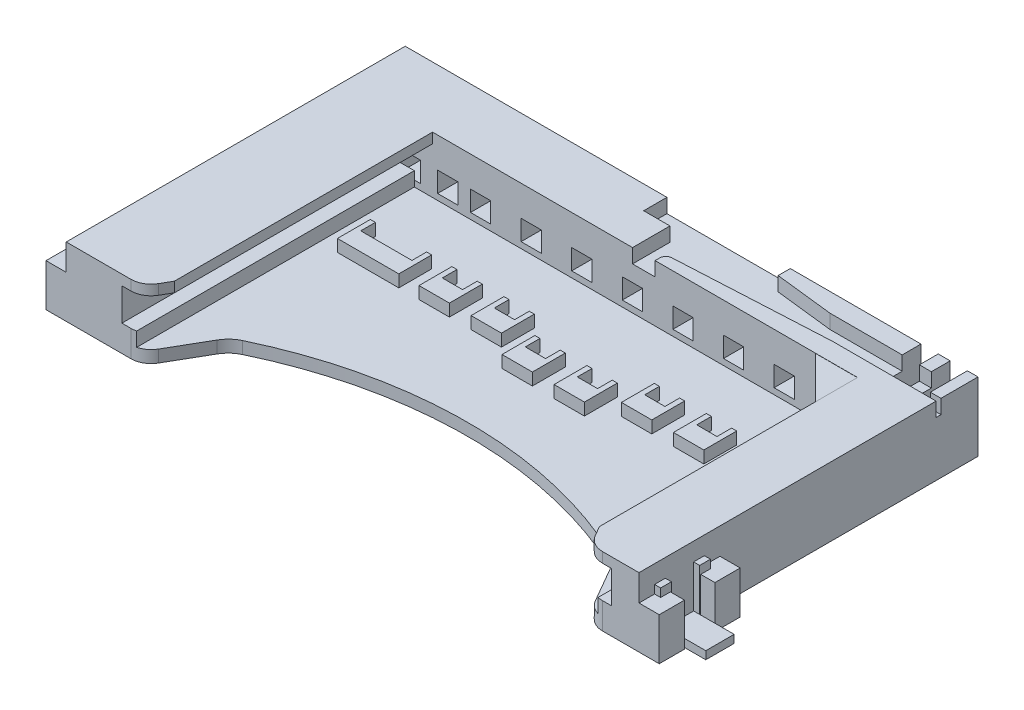
SolidWorks part; units mm, degrees
ref_plane "Front Plane" through (0, 0, 0) normal (0, 0, 1) x (1, 0, 0)
ref_plane "Top Plane" through (0, 0, 0) normal (0, 1, 0) x (1, 0, 0)
ref_plane "Right Plane" through (0, 0, 0) normal (1, 0, 0) x (0, 0, -1)
sketch "Esboço1" plane through (0, 0, 0) normal (0, 1, 0) x (1, 0, 0)
  line L0 (-10.7865, 26.2786) -> (-9.7275, 28.1126)
  line L1 (-14.85, 25.7786) -> (-11.6525, 25.7786)
  line L2 (-14.85, 25.7786) -> (-14.85, 42.5286)
  line L3 (-14.85, 42.5286) -> (13.45, 42.5286)
  line L4 (13.45, 25.7786) -> (13.45, 42.5286)
  line L5 (10.7865, 26.2786) -> (9.7275, 28.1126)
  line L12 (11.6525, 25.7786) -> (13.45, 25.7786)
  arc A0 (-11.6525, 25.7786) -> (-10.7865, 26.2786) centre (-11.6525, 26.7786) ccw
  arc A1 (-9.7275, 28.1126) -> (-9.0765, 28.7156) centre (-8.4283, 27.3629) cw
  arc A2 (9.7275, 28.1126) -> (9.0765, 28.7156) centre (8.4283, 27.3629) ccw
  arc A3 (11.6525, 25.7786) -> (10.7865, 26.2786) centre (11.6525, 26.7786) cw
  arc A4 (-9.0765, 28.7156) -> (9.0765, 28.7156) centre (0, 9.7784) cw
  dimension "D20" = 1
  dimension "D21" = 1
  dimension "D22" = 1.5
  dimension "D23" = 1.5
  dimension "D24" = 21
  dimension "D1" = 14.85
  dimension "D2" = 13.45
  dimension "D3" = 16.75
  dimension "D4" = 3.1975
  dimension "D5" = 1.7975
  dimension "D6" = 0.5
  dimension "D7" = 0.866
  dimension "D8" = 0.866
  dimension "D9" = 0.5
  dimension "D10" = 1.834
  dimension "D11" = 1.834
  dimension "D12" = 1.059
  dimension "D13" = 1.059
  dimension "D14" = 0.603
  dimension "D15" = 0.603
  dimension "D16" = 0.651
  dimension "D17" = 0.651
extrude "Ressalto-extrusão1" add sketch "Esboço1" along normal blind 3.4 separate body
sketch "Esboço2" plane through (0, 0, -25.7786) normal (0, 0, 1) x (1, 0, 0)
  line L0 (-14.85, 3.4) -> (-14.85, 0) construction
  line L1 (-11.4, 0.6) -> (11.4, 0.6)
  line L2 (-11.4, 0.6) -> (-11.4, 1.3)
  line L4 (11.4, 0.6) -> (11.4, 1.3)
  line L5 (-9.0765, 0) -> (9.0765, 0) construction
  line L6 (11.4, 1.3) -> (12.1, 1.3)
  line L7 (-12.1, 2.9) -> (12.1, 2.9)
  line L8 (-12.1, 2.9) -> (-12.1, 1.3)
  line L9 (-12.1, 1.3) -> (-11.4, 1.3)
  line L10 (12.1, 2.9) -> (12.1, 1.3)
  dimension "D1" = 3.45
  dimension "D2" = 0.6
  dimension "D3" = 0.7
  dimension "D4" = 22.8
  dimension "D5" = 24.2
  dimension "D6" = 0.7
  dimension "D7" = 1.6
extrude "Corte-extrusão1" cut sketch "Esboço2" against normal blind 13.75
sketch "Esboço3" plane through (0, 3.4, 0) normal (0, 1, 0) x (1, 0, 0)
  line L0 (-14.85, 25.7786) -> (-11.6525, 25.7786) construction
  line L1 (-10.5, 25.7786) -> (10.5, 25.7786)
  line L2 (-10.5, 25.7786) -> (-10.5, 39.5286)
  line L3 (-10.5, 39.5286) -> (8.42, 39.5286)
  line L4 (10.5, 25.7786) -> (10.5, 37.4486)
  line L5 (-14.85, 42.5286) -> (-14.85, 25.7786) construction
  line L6 (10.5, 37.4486) -> (8.42, 39.5286)
  dimension "D1" = 13.75
  dimension "D2" = 21
  dimension "D3" = 4.35
  dimension "D4" = 2.08
  dimension "D5" = 2.08
extrude "Corte-extrusão2" cut sketch "Esboço3" against normal blind 1
sketch "Esboço4" plane through (13.45, 0, 0) normal (1, 0, 0) x (0, 0, -1)
  line L0 (25.7786, 0) -> (42.5286, 0) construction
  line L1 (25.7786, 0) -> (27.0286, 0)
  line L2 (25.7786, 0) -> (25.7786, 2.1)
  line L3 (25.7786, 2.1) -> (27.0286, 2.1)
  line L4 (27.0286, 0) -> (27.0286, 2.1)
  line L5 (28.5286, 2.1) -> (29.7786, 2.1)
  line L6 (28.5286, 2.1) -> (28.5286, 0)
  line L7 (28.5286, 0) -> (29.7786, 0)
  line L8 (29.7786, 2.1) -> (29.7786, 0)
  dimension "D1" = 2.1
  dimension "D2" = 1.25
  dimension "D3" = 1.5
  dimension "D4" = 1.25
extrude "Ressalto-extrusão2" add sketch "Esboço4" along normal blind 1
sketch "Esboço5" plane through (13.45, 0, 0) normal (1, 0, 0) x (0, 0, -1)
  line L0 (27.0286, 0) -> (28.5286, 0) construction
  line L1 (26.5486, 2.51) -> (27.0786, 2.51)
  line L2 (26.5486, 2.51) -> (26.5486, 0)
  line L3 (26.5486, 0) -> (27.0786, 0)
  line L4 (27.0786, 2.51) -> (27.0786, 0)
  line L5 (27.0286, 2.1) -> (25.7786, 2.1) construction
  line L6 (27.0286, 0) -> (27.0286, 2.1) construction
  line L7 (28.5286, 0) -> (29.7786, 0) construction
  line L8 (28.4786, 2.51) -> (29.0086, 2.51)
  line L9 (28.4786, 2.51) -> (28.4786, 0)
  line L10 (28.4786, 0) -> (29.0086, 0)
  line L11 (29.0086, 2.51) -> (29.0086, 0)
  line L13 (28.5286, 2.1) -> (28.5286, 0) construction
  dimension "D1" = 0.53
  dimension "D2" = 0.41
  dimension "D3" = 0.05
  dimension "D4" = 0.53
  dimension "D5" = 0.05
extrude "Ressalto-extrusão3" add sketch "Esboço5" along normal blind 0.3
sketch "Esboço6" plane through (13.45, 0, 0) normal (1, 0, 0) x (0, 0, -1)
  line L0 (28.4786, 2.51) -> (28.4786, 0) construction
  line L1 (27.0786, 0) -> (28.4786, 0) construction
  line L2 (27.0786, 0.02) -> (27.0786, 0.41)
  line L3 (27.0786, 0.41) -> (28.4786, 0.41)
  line L4 (28.4786, 0.02) -> (28.4786, 0.41)
  line L5 (27.0786, 0.02) -> (28.4786, 0.02)
  dimension "D1" = 0.39
  dimension "D2" = 0.02
extrude "Ressalto-extrusão4" add sketch "Esboço6" along normal blind 2
ref_plane "Plano1" through (-0.7, 0, 0) normal (-1, 0, 0) x (0, 0, 1)
mirror "Espelhar1" about plane through (-0.7, 0, 0) normal (-1, 0, 0) of "Ressalto-extrusão2"
mirror "Espelhar2" about plane through (-0.7, 0, 0) normal (-1, 0, 0) of "Ressalto-extrusão3", "Ressalto-extrusão4"
sketch "Esboço7" plane through (0, 0, 0) normal (0, -1, 0) x (-1, 0, 0)
  line L0 (-13.45, 29.7786) -> (-13.45, 42.5286) construction
  line L1 (-13.45, 42.5286) -> (14.85, 42.5286) construction
  line L2 (14.85, 42.5286) -> (14.85, 29.7786) construction
  circle A0 centre (-11.95, 41.0286) radius 0.75
  circle A1 centre (13.35, 41.0286) radius 0.75
  dimension "D1" = 1.5
  dimension "D2" = 1.5
  dimension "D3" = 1.5
  dimension "D5" = 1.5
  dimension "D4" = 1.5
extrude "Ressalto-extrusão5" add sketch "Esboço7" along normal blind 0.8
fillet "Filete1" radius 0.3 2 edges at (11.95, -0.8, -41.7786) (-13.35, -0.8, -41.7786)
sketch "Esboço8" plane through (0, 0.6, 0) normal (0, 1, 0) x (1, 0, 0)
  line L0 (-10.5, 39.5286) -> (-10.5, 26.7747) construction
  line L1 (-10.5, 36.4536) -> (-10.25, 36.4536)
  line L2 (-10.5, 36.4536) -> (-10.5, 34.8286)
  line L3 (-10.5, 34.8286) -> (-7.4686, 34.8286)
  line L4 (-7.4686, 36.4536) -> (-7.4686, 34.8286)
  line L5 (8.42, 39.5286) -> (-10.5, 39.5286) construction
  line L6 (-7.7186, 36.4536) -> (-7.4686, 36.4536)
  line L8 (-10.25, 36.4536) -> (-10.25, 35.7286)
  line L9 (-10.25, 35.7286) -> (-7.7186, 35.7286)
  line L10 (-7.7186, 36.4536) -> (-7.7186, 35.7286)
  dimension "D1" = 4.7
  dimension "D2" = 1.625
  dimension "D3" = 0.725
  dimension "D4" = 0.25
  dimension "D5" = 0.25
extrude "Ressalto-extrusão6" add sketch "Esboço8" along normal blind 0.6
sketch "Esboço9" plane through (0, 0.6, 0) normal (0, 1, 0) x (1, 0, 0)
  line L0 (-7.4686, 34.8286) -> (-7.4686, 36.4536) construction
  line L1 (-6.4686, 34.8286) -> (-4.9686, 34.8286)
  line L2 (-6.4686, 34.8286) -> (-6.4686, 36.4536)
  line L3 (-6.4686, 36.4536) -> (-6.2186, 36.4536)
  line L4 (-4.9686, 34.8286) -> (-4.9686, 36.4536)
  line L5 (-5.2186, 36.4536) -> (-4.9686, 36.4536)
  line L7 (-6.2186, 36.4536) -> (-6.2186, 35.7286)
  line L8 (-6.2186, 35.7286) -> (-5.2186, 35.7286)
  line L9 (-5.2186, 36.4536) -> (-5.2186, 35.7286)
  dimension "D1" = 1.5
  dimension "D2" = 1
  dimension "D3" = 0.25
  dimension "D4" = 0.25
extrude "Ressalto-extrusão7" add sketch "Esboço9" along normal blind 0.6
pattern_linear "Padrão linear1" count 2 spacing 2.571 along (1, 0, 0) of "Ressalto-extrusão7"
pattern_linear "Padrão linear2" count 2 spacing 10 along (1, 0, 0) of "Ressalto-extrusão7", "Padrão linear1"
pattern_linear "Padrão linear3" count 2 spacing 5 along (1, 0, 0) count 2 spacing 0.9 along (0, 0, 1) skipping (0, 1), (1, 0) of "Ressalto-extrusão7", "Padrão linear1"
pattern_linear "Padrão linear4" count 2 spacing 15 along (1, 0, 0) count 2 spacing 2.8 along (0, 0, 1) skipping (0, 1), (1, 0) of "Ressalto-extrusão7"
sketch "Esboço10" plane through (0, 3.4, 0) normal (0, 1, 0) x (1, 0, 0)
  line L1 (8.42, 39.5286) -> (10.5, 39.5286)
  line L2 (8.42, 39.5286) -> (8.42, 37.4486)
  line L3 (8.42, 37.4486) -> (10.5, 37.4486)
  line L4 (10.5, 39.5286) -> (10.5, 37.4486)
extrude "Corte-extrusão3" cut sketch "Esboço10" against normal blind 0.01
sketch "Esboço11" plane through (0, 3.4, 0) normal (0, 1, 0) x (1, 0, 0)
  line L0 (-1.92, 42.5286) -> (-1.92, 41.3786)
  line L1 (13.45, 42.5286) -> (-14.85, 42.5286) construction
  line L2 (-1.92, 41.3786) -> (-0.62, 41.3786)
  line L3 (-0.62, 41.3786) -> (-0.62, 38.8912)
  line L4 (-0.62, 38.8912) -> (0.495, 38.8912)
  line L5 (0.495, 38.8912) -> (0.495, 39.7622)
  line L6 (0.7793, 40.0618) -> (8.3503, 40.4586)
  line L7 (8.3503, 40.4586) -> (12.9246, 40.4586)
  line L8 (12.9246, 40.4586) -> (12.9246, 41.5986)
  line L9 (12.9246, 41.5986) -> (7.071, 41.5986)
  line L10 (7.071, 41.5986) -> (4.175, 41.9286)
  line L11 (4.175, 41.9286) -> (4.175, 43.073)
  line L12 (4.175, 43.073) -> (-1.92, 42.5286)
  line L13 (-14.85, 42.5286) -> (-14.85, 25.7786) construction
  line L17 (10.5, 39.5286) -> (-10.5, 39.5286) construction
  arc A0 (0.495, 39.7622) -> (0.7793, 40.0618) centre (0.795, 39.7622) cw
  dimension "D9" = 0.3
  dimension "D1" = 12.93
  dimension "D2" = 1.3
  dimension "D3" = 1.115
  dimension "D4" = 6.095
  dimension "D5" = 2.896
  dimension "D6" = 0.33
  dimension "D7" = 5.8536
  dimension "D8" = 0.6
  dimension "D10" = 0.2336
  dimension "D11" = 7.571
  dimension "D12" = 0.3968
  dimension "D13" = 1.15
extrude "Corte-extrusão4" cut sketch "Esboço11" against normal blind 0.7
sketch "Esboço12" plane through (0, 3.4, 0) normal (0, 1, 0) x (1, 0, 0)
  line L0 (8.3503, 40.4586) -> (12.9246, 40.4586) construction
  line L1 (12.9246, 40.4586) -> (12.0746, 40.4586)
  line L2 (12.9246, 40.4586) -> (12.9246, 43.4689)
  line L3 (12.9246, 43.4689) -> (12.0746, 43.4689)
  line L4 (12.0746, 40.4586) -> (12.0746, 43.4689)
  line L5 (11.4846, 40.4586) -> (10.6346, 40.4586)
  line L6 (11.4846, 40.4586) -> (11.4846, 43.6068)
  line L7 (11.4846, 43.6068) -> (10.6346, 43.6068)
  line L8 (10.6346, 40.4586) -> (10.6346, 43.6068)
  dimension "D1" = 0.85
  dimension "D2" = 0.59
  dimension "D3" = 0.85
extrude "Corte-extrusão5" cut sketch "Esboço12" against normal blind 2.5
ref_plane "Plano2" through (-0.7, 0, 0) normal (-1, 0, 0) x (0, 0, 1)
sketch "Esboço14" plane through (0, 0, -42.5286) normal (0, 0, -1) x (-1, 0, 0)
  line L0 (14.85, 0) -> (14.85, 2.1) construction
  line L1 (8.625, 0.9) -> (7.625, 0.9)
  line L2 (8.625, 0.9) -> (8.625, 1.9)
  line L3 (8.625, 1.9) -> (7.625, 1.9)
  line L4 (7.625, 0.9) -> (7.625, 1.9)
  line L5 (-13.45, 0) -> (14.85, 0) construction
  dimension "D1" = 1
  dimension "D2" = 1
  dimension "D3" = 6.225
  dimension "D4" = 0.9
extrude "Corte-extrusão6" cut sketch "Esboço14" against normal up to surface (3 mm away) up to face at (0.9217, 2.4322, -39.5286)
pattern_linear "Padrão linear5" count 8 spacing 2.5 along (1, 0, 0) of "Corte-extrusão6"
pattern_linear "Padrão linear6" count 2 spacing 1.625 along (-1, 0, 0) of "Corte-extrusão6"
pattern_linear "Padrão linear7" count 2 spacing 3.47 along (-1, 0, 0) of "Corte-extrusão6"
pattern_linear "Padrão linear8" count 2 spacing 5.12 along (-1, 0, 0) of "Corte-extrusão6"
sketch "Esboço15" plane through (0, 3.4, 0) normal (0, 1, 0) x (1, 0, 0)
  line L0 (13.45, 25.7786) -> (13.45, 42.5286) construction
  line L1 (12.9246, 40.4586) -> (13.45, 40.4586)
  line L2 (12.9246, 40.4586) -> (12.9246, 40.6986)
  line L3 (12.9246, 40.6986) -> (13.45, 40.6986)
  line L4 (13.45, 40.4586) -> (13.45, 40.6986)
  dimension "D1" = 0.24
extrude "Corte-extrusão7" cut sketch "Esboço15" against normal blind 0.7
